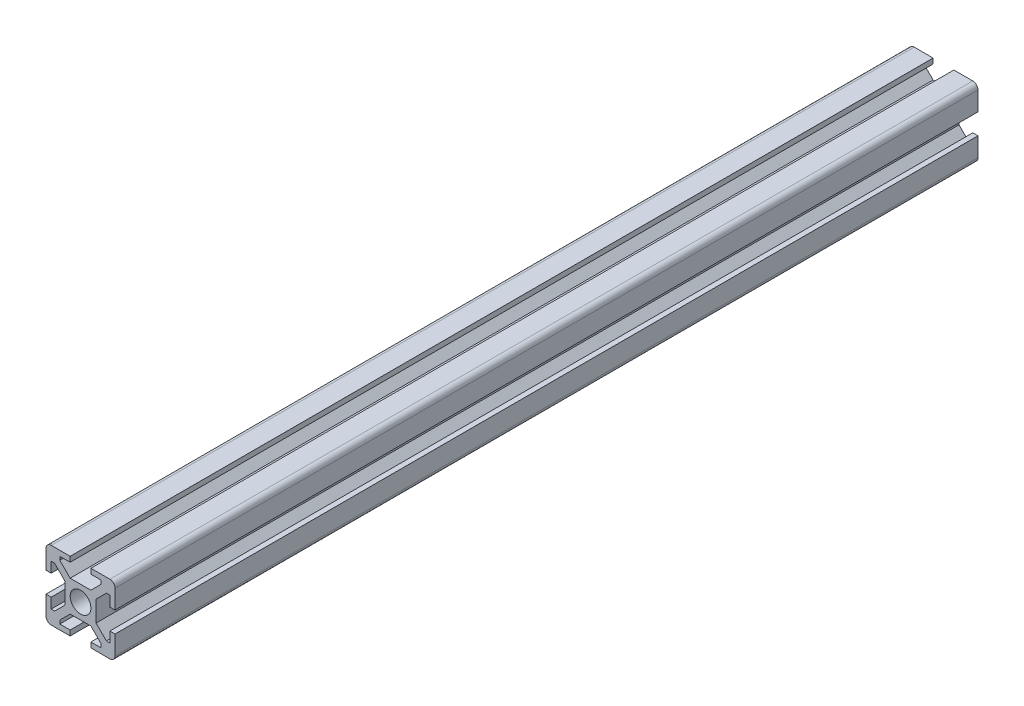
SolidWorks part; units mm, degrees
ref_plane "Plan de face" through (0, 0, 0) normal (0, 0, 1) x (1, 0, 0)
ref_plane "Plan de dessus" through (0, 0, 0) normal (0, 1, 0) x (1, 0, 0)
ref_plane "Plan de droite" through (0, 0, 0) normal (1, 0, 0) x (0, 0, -1)
sketch "Esquisse1" plane through (0, 0, 0) normal (0, 0, 1) x (1, 0, 0)
  line L0 (-10, 10) -> (10, -10) construction
  line L1 (-10, 10) -> (10, 10)
  line L2 (-10, 10) -> (-10, -10)
  line L3 (-10, -10) -> (10, -10)
  line L4 (10, 10) -> (10, -10)
  dimension "D1" = 20
extrude "Extrusion1" add sketch "Esquisse1" along normal mid plane 250
fillet "Congé1" radius 1.5 4 edges at (-10, -10, 0) (10, -10, 0) (-10, 10, 0) (10, 10, 0)
sketch "Esquisse2" plane through (0, 0, -125) normal (0, 0, -1) x (-1, 0, 0)
  line L0 (-10, 3) -> (-10, -3)
  line L1 (-10, -8.5) -> (-10, 8.5) construction
  line L2 (-10, -3) -> (-8.5, -3)
  line L3 (-8.5, -3) -> (-8.5, -6)
  line L4 (-8.5, 6) -> (-7.5, 6)
  line L5 (-4.5, -3) -> (-4.5, 3)
  line L6 (-7.5, 6) -> (-4.5, 3)
  line L7 (-8.5, 6) -> (-8.5, 3)
  line L8 (-8.5, 3) -> (-10, 3)
  line L9 (0, 0) -> (-10, 0) construction
  line L10 (-8.5, -6) -> (-7.5, -6)
  line L11 (-7.5, -6) -> (-4.5, -3)
  point P4 (-10, 0)
  dimension "D1" = 6
  dimension "D2" = 12
  dimension "D3" = 1.5
  dimension "D4" = 5.5
  dimension "D5" = 135
extrude "Enlèv. mat.-Extru.1" cut sketch "Esquisse2" against normal through all
ref_axis "Axe1" through (0, 0, 9.3338) along (0, 0, -1)
pattern_circular "Répétition circulaire1" count 4 over 360 about axis through (0, 0, 9.3338) along (0, 0, -1) of "Enlèv. mat.-Extru.1"
hole_wizard "Trou taraudé M6x1.01" positions "Esquisse4" profile "Esquisse5" tap size "M6x1.0" standard "Ansi Métrique"
sketch "Esquisse4" plane through (0, 0, -125) normal (0, 0, -1) x (-1, 0, 0)
  point P0 (0, 0)
sketch "Esquisse5" plane through (0, 0, -125) normal (1, 0, 0) x (0, 1, 0)
  line L0 (0, 0) -> (0, 31.5022)
  line L1 (0, 31.5022) -> (2.5, 30)
  line L2 (2.5, 30) -> (2.5, 24)
  line L3 (2.5, 24) -> (3, 24)
  line L4 (3, 24) -> (3, 0)
  line L5 (3, 0) -> (0, 0)
  line L10 (0, 31.5022) -> (-2.5, 30) construction
  line L11 (0, -6.35) -> (0, 107.95) construction
  dimension "Diamètre du trou pour taraudage" = 5
  dimension "Profondeur du trou pour taraudage" = 30
  dimension "Diamètre principal du filetage" = 6
  dimension "Profondeur du filetage" = 24
  dimension "Angle de pointe" = 118
mirror "Symétrie1" about plane through (0, 0, 0) normal (0, 0, 1) of "Trou taraudé M6x1.01"
